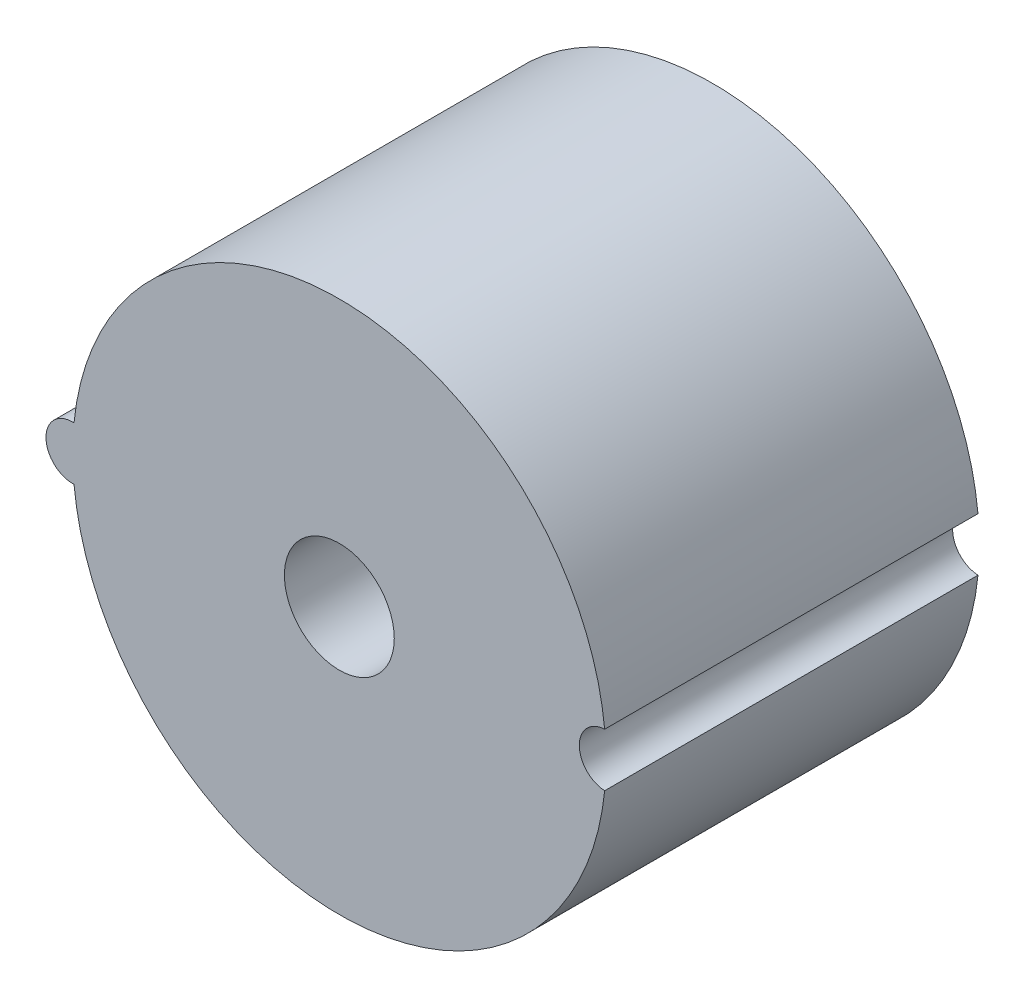
SolidWorks part; units mm, degrees
material "PET"
ref_plane "Front" through (0, 0, 0) normal (0, 0, 1) x (1, 0, 0)
ref_plane "Top" through (0, 0, 0) normal (0, 1, 0) x (1, 0, 0)
ref_plane "Right" through (0, 0, 0) normal (1, 0, 0) x (0, 0, -1)
sketch "Sketch1" plane through (0, 0, 0) normal (0, 0, 1) x (1, 0, 0)
  circle A0 centre (0, 0) radius 10.541 construction
  circle A1 centre (0, 0) radius 10.795
  circle A2 centre (0, 0) radius 15.875
  circle A3 centre (0, 0) radius 3.175
  circle A4 centre (0, 0) radius 5.08
  dimension "D1" = 0.254
  dimension "." = 21.082
  dimension "D2" = 31.75
  dimension "D3" = 6.35
  dimension "D4" = 10.16
extrude "Boss-Extrude1" add sketch "Sketch1" along normal blind 22.225 contours A2
extrude "Cut-Extrude1" cut sketch "Sketch1<3>" along normal blind 5.08 contours A1
sketch "Sketch1<3>" plane through (0, 0, 0) normal (0, 0, 1) x (1, 0, 0) same geometry as "Sketch1"
extrude "Boss-Extrude2" add sketch "Sketch1<4>" against normal blind 0.889 from surface contours A4 starting at face at (10.795, 0, 5.08)
sketch "Sketch1<4>" plane through (0, 0, 0) normal (0, 0, 1) x (1, 0, 0) same geometry as "Sketch1"
extrude "Boss-Extrude3" add sketch "Sketch1<5>" against normal blind 6.35 from surface contours A3 starting at face at (5.08, 0, 5.08)
sketch "Sketch1<5>" plane through (0, 0, 0) normal (0, 0, 1) x (1, 0, 0) same geometry as "Sketch1"
sketch "Sketch2" plane through (0, 0, 22.225) normal (0, 0, 1) x (1, 0, 0)
  circle A0 centre (0, 0) radius 3.2703
  dimension "D1" = 6.5405
extrude "Cut-Extrude2" cut sketch "Sketch2" against normal blind 12.7
sketch "Sketch3" plane through (0, 0, 22.225) normal (0, 0, 1) x (1, 0, 0)
  line L0 (-15.875, 0) -> (0, 0) construction
  line L1 (0, 0) -> (15.875, 0) construction
  circle A0 centre (15.875, 0) radius 1.5875
  circle A1 centre (0, 0) radius 15.875 construction
  circle A2 centre (-15.875, 0) radius 1.5875
  dimension "D1" = 3.175
  dimension "D2" = 3.175
extrude "Cut-Extrude4" cut sketch "Sketch3" against normal through all contours A0
extrude "Boss-Extrude4" add sketch "Sketch3<3>" against normal up to surface (22.225 mm away) contours A2 up to face at (10.795, 0, 0)
sketch "Sketch3<3>" plane through (0, 0, 22.225) normal (0, 0, 1) x (1, 0, 0) same geometry as "Sketch3"
